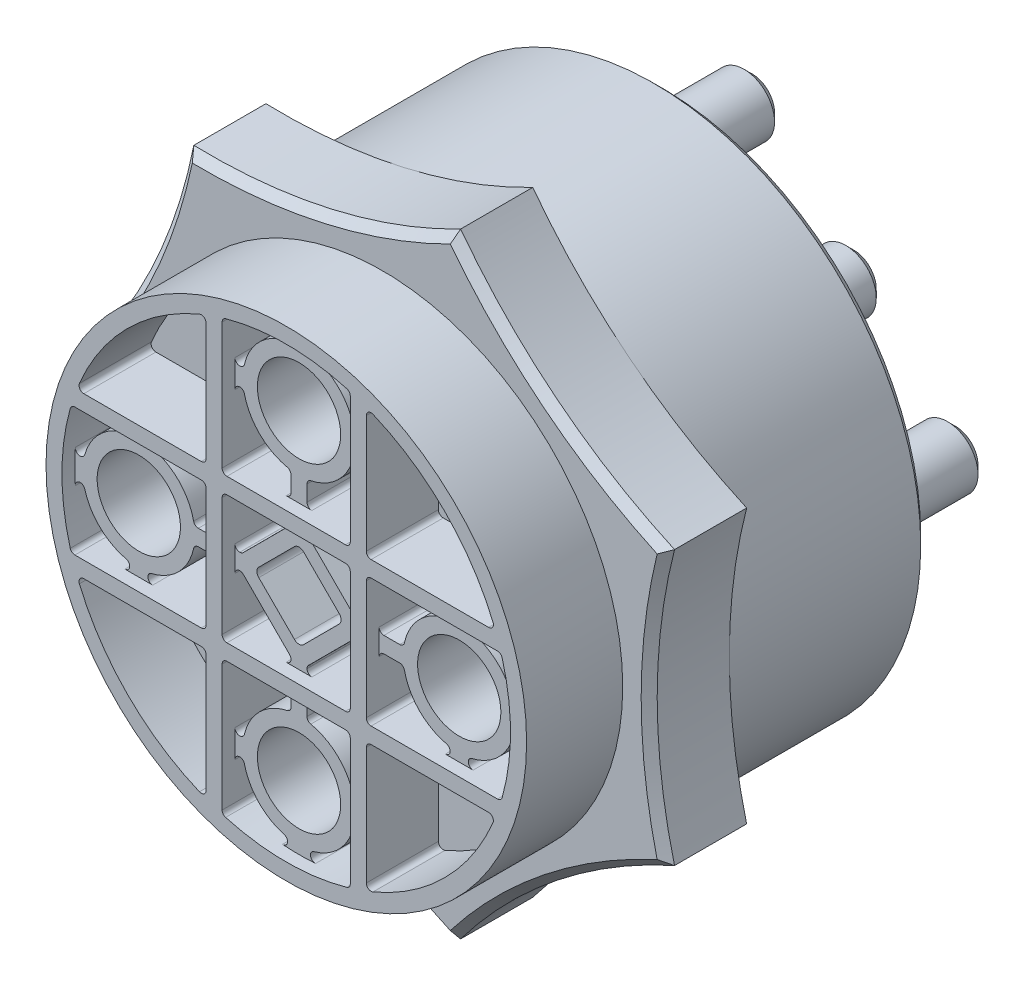
SolidWorks part; units mm, degrees
ref_plane "Front Plane" through (0, 0, 0) normal (0, 0, 1) x (1, 0, 0)
ref_plane "Top Plane" through (0, 0, 0) normal (0, 1, 0) x (1, 0, 0)
ref_plane "Right Plane" through (0, 0, 0) normal (1, 0, 0) x (0, 0, -1)
sketch "Sketch1" plane through (0, 0, 0) normal (0, 0, 1) x (1, 0, 0)
  circle A0 centre (0, 0) radius 16.85 construction
  circle A1 centre (0, 0) radius 16.65
  arc A2 (3.175, -6.35) -> (9.525, -6.35) centre (6.35, -6.35) ccw construction
  arc A3 (0, -15.875) -> (0, -9.525) centre (0, -12.7) ccw construction
  arc A4 (0, 4) -> (0, -4) centre (0, 0) ccw construction
  arc A5 (-6.35, -9.525) -> (-6.35, -3.175) centre (-6.35, -6.35) ccw construction
  arc A6 (-12.7, -3.175) -> (-12.7, 3.175) centre (-12.7, 0) ccw construction
  arc A7 (-6.35, 3.175) -> (-6.35, 9.525) centre (-6.35, 6.35) ccw construction
  arc A8 (15.875, 0) -> (9.525, 0) centre (12.7, 0) ccw construction
  arc A9 (9.525, 6.35) -> (3.175, 6.35) centre (6.35, 6.35) ccw construction
  arc A10 (3.175, 12.7) -> (-3.175, 12.7) centre (0, 12.7) ccw construction
  circle A11 centre (6.35, -6.35) radius 3.175 construction
  circle A12 centre (0, -12.7) radius 3.175 construction
  circle A13 centre (0, 0) radius 4 construction
  circle A14 centre (-6.35, -6.35) radius 3.175 construction
  circle A15 centre (-12.7, 0) radius 3.175 construction
  circle A16 centre (-6.35, 6.35) radius 3.175 construction
  circle A17 centre (12.7, 0) radius 3.175 construction
  circle A18 centre (6.35, 6.35) radius 3.175 construction
  circle A19 centre (0, 12.7) radius 3.175 construction
  circle A20 centre (-6.35, 6.35) radius 3.275
  circle A21 centre (-12.7, 0) radius 3.275
  circle A22 centre (-6.35, -6.35) radius 3.275
  circle A23 centre (0, 0) radius 4.1
  circle A24 centre (0, 12.7) radius 3.275
  circle A25 centre (6.35, 6.35) radius 3.275
  circle A26 centre (12.7, 0) radius 3.275
  circle A27 centre (6.35, -6.35) radius 3.275
  circle A28 centre (0, -12.7) radius 3.275
  arc A29 (-12.4359, 15.5945) -> (4.4391, 19.4457) centre (-11.3095, 49.5559) ccw construction
  dimension "D1" = 0.2
  dimension "D2" = 0.1
extrude "Boss-Extrude1" add sketch "Sketch1" along normal offset from surface (2.375 mm away) 0.2 offset beyond the face yes
sketch "Sketch2" plane through (0, 0, 2.375) normal (0, 0, 1) x (1, 0, 0)
  circle A0 centre (0, 0) radius 16.65 construction
  circle A1 centre (0, 0) radius 16.65
extrude "Boss-Extrude2" add sketch "Sketch2" along normal up to surface (22.075 mm away)
sketch "Sketch3" plane through (0, 0, 24.45) normal (0, 0, 1) x (1, 0, 0)
  circle A0 centre (0, 0) radius 15
  circle A1 centre (0, 0) radius 16.65 construction
  circle A2 centre (0, 0) radius 16.65
  dimension "D1" = 30
extrude "Cut-Extrude1" cut sketch "Sketch3" against normal blind 10
sketch "Sketch4" plane through (0, 0, 24.45) normal (0, 0, 1) x (1, 0, 0)
  line L0 (-13.1976, -3.971) -> (-5.3067, -3.971)
  line L1 (-5.3067, 4.029) -> (-13.1976, 4.029)
  line L2 (-5.0067, -3.671) -> (-5.0067, 3.729)
  line L3 (-12.64, 5.029) -> (-5.3067, 5.029)
  line L4 (-5.0067, 5.329) -> (-5.0067, 12.6623)
  line L5 (-5.3067, -4.971) -> (-12.64, -4.971)
  line L6 (-5.0067, -12.6043) -> (-5.0067, -5.271)
  line L7 (3.9933, -13.1619) -> (3.9933, -5.271)
  line L8 (-4.0067, -5.271) -> (-4.0067, -13.1619)
  line L9 (3.6933, -4.971) -> (-3.7067, -4.971)
  line L10 (-3.7067, -3.971) -> (3.6933, -3.971)
  line L11 (-4.0067, 3.729) -> (-4.0067, -3.671)
  line L12 (3.6933, 4.029) -> (-3.7067, 4.029)
  line L13 (3.9933, -3.671) -> (3.9933, 3.729)
  line L14 (-3.7067, 5.029) -> (3.6933, 5.029)
  line L15 (-4.0067, 13.2199) -> (-4.0067, 5.329)
  line L16 (3.9933, 5.329) -> (3.9933, 13.2199)
  line L17 (5.2933, 5.029) -> (12.6266, 5.029)
  line L18 (4.9933, 12.6623) -> (4.9933, 5.329)
  line L19 (4.9933, 3.729) -> (4.9933, -3.671)
  line L20 (13.1842, 4.029) -> (5.2933, 4.029)
  line L21 (5.2933, -3.971) -> (13.1842, -3.971)
  line L22 (12.6266, -4.971) -> (5.2933, -4.971)
  line L23 (4.9933, -5.271) -> (4.9933, -12.6043)
  line L24 (5.2933, -0.471) -> (6.2784, -0.471)
  line L25 (4.9933, 0.829) -> (4.9933, -0.771)
  line L26 (6.2784, 0.529) -> (5.2933, 0.529)
  line L27 (10.8593, 4.029) -> (9.1273, 4.029)
  line L28 (9.1273, -3.971) -> (10.8593, -3.971)
  line L29 (0.4933, 5.329) -> (0.4933, 6.3142)
  line L30 (-0.8067, 5.029) -> (0.7933, 5.029)
  line L31 (-0.5067, 6.3142) -> (-0.5067, 5.329)
  line L32 (-4.0067, 10.895) -> (-4.0067, 9.163)
  line L33 (3.9933, 9.163) -> (3.9933, 10.895)
  line L34 (-0.5067, -3.6611) -> (-0.5067, -3.671)
  line L35 (-3.4847, -0.5589) -> (-0.5946, -3.449)
  line L36 (-3.7067, -0.471) -> (-3.6968, -0.471)
  line L37 (-4.0067, 0.829) -> (-4.0067, -0.771)
  line L38 (-3.6968, 0.529) -> (-3.7067, 0.529)
  line L39 (-0.5946, 3.507) -> (-3.4847, 0.6169)
  line L40 (-0.5067, 3.729) -> (-0.5067, 3.7191)
  line L41 (0.7933, 4.029) -> (-0.8067, 4.029)
  line L42 (0.4933, 3.7191) -> (0.4933, 3.729)
  line L43 (3.4713, 0.6169) -> (0.5811, 3.507)
  line L44 (3.6933, 0.529) -> (3.6834, 0.529)
  line L45 (3.9933, -0.771) -> (3.9933, 0.829)
  line L46 (3.6834, -0.471) -> (3.6933, -0.471)
  line L47 (0.5811, -3.449) -> (3.4713, -0.5589)
  line L48 (0.4933, -3.671) -> (0.4933, -3.6611)
  line L49 (-0.8067, -3.971) -> (0.7933, -3.971)
  line L50 (-0.5067, -5.271) -> (-0.5067, -6.2561)
  line L51 (0.7933, -4.971) -> (-0.8067, -4.971)
  line L52 (0.4933, -6.2561) -> (0.4933, -5.271)
  line L53 (3.9933, -10.837) -> (3.9933, -9.105)
  line L54 (-4.0067, -9.105) -> (-4.0067, -10.837)
  line L55 (-5.3067, 0.529) -> (-6.2919, 0.529)
  line L56 (-5.0067, -0.771) -> (-5.0067, 0.829)
  line L57 (-6.2919, -0.471) -> (-5.3067, -0.471)
  line L58 (-10.8727, -3.971) -> (-9.1407, -3.971)
  line L59 (-9.1407, 4.029) -> (-10.8727, 4.029)
  line L60 (-2.4462, -0.1831) -> (-0.2189, -2.4105)
  line L61 (0.2054, -2.4105) -> (2.4328, -0.1831)
  line L62 (2.4328, 0.2411) -> (0.2054, 2.4685)
  line L63 (-0.2189, 2.4685) -> (-2.4462, 0.2411)
  circle A0 centre (0, 0) radius 14 construction
  circle A1 centre (0, 0) radius 15 construction
  arc A2 (-0.0067, 14.929) -> (14.3537, -3.9443) centre (-0.0067, 0.029) ccw
  arc A3 (14.3537, -3.9443) -> (-0.0067, 14.929) centre (-0.0067, 0.029) ccw
  arc A4 (-5.3067, -3.971) -> (-5.0067, -3.671) centre (-5.3067, -3.671) ccw
  arc A5 (-13.4865, -3.752) -> (-13.1976, -3.971) centre (-13.1976, -3.671) ccw
  arc A6 (-13.4865, 3.81) -> (-13.4865, -3.752) centre (-0.0067, 0.029) ccw
  arc A7 (-13.1976, 4.029) -> (-13.4865, 3.81) centre (-13.1976, 3.729) ccw
  arc A8 (-5.0067, 3.729) -> (-5.3067, 4.029) centre (-5.3067, 3.729) ccw
  arc A9 (-12.9166, 5.4451) -> (-12.64, 5.029) centre (-12.64, 5.329) ccw
  arc A10 (-5.4228, 12.9389) -> (-12.9166, 5.4451) centre (-0.0067, 0.029) ccw
  arc A11 (-5.0067, 12.6623) -> (-5.4228, 12.9389) centre (-5.3067, 12.6623) ccw
  arc A12 (-5.3067, 5.029) -> (-5.0067, 5.329) centre (-5.3067, 5.329) ccw
  arc A13 (-5.4228, -12.8809) -> (-5.0067, -12.6043) centre (-5.3067, -12.6043) ccw
  arc A14 (-12.9166, -5.387) -> (-5.4228, -12.8809) centre (-0.0067, 0.029) ccw
  arc A15 (-12.64, -4.971) -> (-12.9166, -5.387) centre (-12.64, -5.271) ccw
  arc A16 (-5.0067, -5.271) -> (-5.3067, -4.971) centre (-5.3067, -5.271) ccw
  arc A17 (3.9933, -5.271) -> (3.6933, -4.971) centre (3.6933, -5.271) ccw
  arc A18 (3.7743, -13.4507) -> (3.9933, -13.1619) centre (3.6933, -13.1619) ccw
  arc A19 (-3.7877, -13.4507) -> (3.7743, -13.4507) centre (-0.0067, 0.029) ccw
  arc A20 (-4.0067, -13.1619) -> (-3.7877, -13.4507) centre (-3.7067, -13.1619) ccw
  arc A21 (-3.7067, -4.971) -> (-4.0067, -5.271) centre (-3.7067, -5.271) ccw
  arc A22 (-4.0067, -3.671) -> (-3.7067, -3.971) centre (-3.7067, -3.671) ccw
  arc A23 (-3.7067, 4.029) -> (-4.0067, 3.729) centre (-3.7067, 3.729) ccw
  arc A24 (3.9933, 3.729) -> (3.6933, 4.029) centre (3.6933, 3.729) ccw
  arc A25 (3.6933, -3.971) -> (3.9933, -3.671) centre (3.6933, -3.671) ccw
  arc A26 (-4.0067, 5.329) -> (-3.7067, 5.029) centre (-3.7067, 5.329) ccw
  arc A27 (-3.7877, 13.5088) -> (-4.0067, 13.2199) centre (-3.7067, 13.2199) ccw
  arc A28 (3.7743, 13.5088) -> (-3.7877, 13.5088) centre (-0.0067, 0.029) ccw
  arc A29 (3.9933, 13.2199) -> (3.7743, 13.5088) centre (3.6933, 13.2199) ccw
  arc A30 (3.6933, 5.029) -> (3.9933, 5.329) centre (3.6933, 5.329) ccw
  arc A31 (5.4093, 12.9389) -> (4.9933, 12.6623) centre (5.2933, 12.6623) ccw
  arc A32 (12.9032, 5.4451) -> (5.4093, 12.9389) centre (-0.0067, 0.029) ccw
  arc A33 (12.6266, 5.029) -> (12.9032, 5.4451) centre (12.6266, 5.329) ccw
  arc A34 (4.9933, 5.329) -> (5.2933, 5.029) centre (5.2933, 5.329) ccw
  arc A35 (5.2933, 4.029) -> (4.9933, 3.729) centre (5.2933, 3.729) ccw
  arc A36 (13.473, 3.81) -> (13.1842, 4.029) centre (13.1842, 3.729) ccw
  arc A37 (13.473, -3.752) -> (13.473, 3.81) centre (-0.0067, 0.029) ccw
  arc A38 (13.1842, -3.971) -> (13.473, -3.752) centre (13.1842, -3.671) ccw
  arc A39 (4.9933, -3.671) -> (5.2933, -3.971) centre (5.2933, -3.671) ccw
  arc A40 (12.9032, -5.387) -> (12.6266, -4.971) centre (12.6266, -5.271) ccw
  arc A41 (5.4093, -12.8809) -> (12.9032, -5.387) centre (-0.0067, 0.029) ccw
  arc A42 (4.9933, -12.6043) -> (5.4093, -12.8809) centre (5.2933, -12.6043) ccw
  arc A43 (5.2933, -4.971) -> (4.9933, -5.271) centre (5.2933, -5.271) ccw
  circle A44 centre (-0.0067, -9.971) radius 2.5
  circle A45 centre (-10.0067, 0.029) radius 2.5
  circle A46 centre (9.9933, 0.029) radius 2.5
  circle A47 centre (-0.0067, 10.029) radius 2.5
  arc A48 (5.2933, -0.471) -> (4.9933, -0.771) centre (5.2933, -0.771) ccw
  arc A49 (4.9933, 0.829) -> (5.2933, 0.529) centre (5.2933, 0.829) ccw
  arc A50 (6.2784, 0.529) -> (6.5717, 0.7659) centre (6.2784, 0.829) ccw
  arc A51 (9.1956, 3.4369) -> (6.5717, 0.7659) centre (9.9933, 0.029) ccw
  arc A52 (9.1956, 3.4369) -> (9.1273, 4.029) centre (9.1273, 3.729) ccw
  arc A53 (10.8593, 4.029) -> (10.7909, 3.4369) centre (10.8593, 3.729) ccw
  arc A54 (13.3666, 0.962) -> (10.7909, 3.4369) centre (9.9933, 0.029) ccw
  arc A55 (13.3666, 0.962) -> (13.955, 1.0642) centre (13.6558, 1.042) ccw
  arc A56 (13.955, -1.0061) -> (13.955, 1.0642) centre (-0.0067, 0.029) ccw
  arc A57 (13.955, -1.0061) -> (13.3666, -0.904) centre (13.6558, -0.9839) ccw
  arc A58 (10.7909, -3.3789) -> (13.3666, -0.904) centre (9.9933, 0.029) ccw
  arc A59 (10.7909, -3.3789) -> (10.8593, -3.971) centre (10.8593, -3.671) ccw
  arc A60 (9.1273, -3.971) -> (9.1956, -3.3789) centre (9.1273, -3.671) ccw
  arc A61 (6.5717, -0.7078) -> (9.1956, -3.3789) centre (9.9933, 0.029) ccw
  arc A62 (6.5717, -0.7078) -> (6.2784, -0.471) centre (6.2784, -0.771) ccw
  arc A63 (-0.5067, -3.6611) -> (-0.5946, -3.449) centre (-0.8067, -3.6611) ccw
  arc A64 (-3.4847, -0.5589) -> (-3.6968, -0.471) centre (-3.6968, -0.771) ccw
  arc A65 (-3.7067, -0.471) -> (-4.0067, -0.771) centre (-3.7067, -0.771) ccw
  arc A66 (-4.0067, 0.829) -> (-3.7067, 0.529) centre (-3.7067, 0.829) ccw
  arc A67 (-3.6968, 0.529) -> (-3.4847, 0.6169) centre (-3.6968, 0.829) ccw
  arc A68 (-0.5946, 3.507) -> (-0.5067, 3.7191) centre (-0.8067, 3.7191) ccw
  arc A69 (-0.5067, 3.729) -> (-0.8067, 4.029) centre (-0.8067, 3.729) ccw
  arc A70 (0.7933, 4.029) -> (0.4933, 3.729) centre (0.7933, 3.729) ccw
  arc A71 (0.4933, 3.7191) -> (0.5811, 3.507) centre (0.7933, 3.7191) ccw
  arc A72 (3.4713, 0.6169) -> (3.6834, 0.529) centre (3.6834, 0.829) ccw
  arc A73 (3.6933, 0.529) -> (3.9933, 0.829) centre (3.6933, 0.829) ccw
  arc A74 (3.9933, -0.771) -> (3.6933, -0.471) centre (3.6933, -0.771) ccw
  arc A75 (3.6834, -0.471) -> (3.4713, -0.5589) centre (3.6834, -0.771) ccw
  arc A76 (0.5811, -3.449) -> (0.4933, -3.6611) centre (0.7933, -3.6611) ccw
  arc A77 (0.4933, -3.671) -> (0.7933, -3.971) centre (0.7933, -3.671) ccw
  arc A78 (-0.8067, -3.971) -> (-0.5067, -3.671) centre (-0.8067, -3.671) ccw
  arc A79 (0.4933, 5.329) -> (0.7933, 5.029) centre (0.7933, 5.329) ccw
  arc A80 (-0.8067, 5.029) -> (-0.5067, 5.329) centre (-0.8067, 5.329) ccw
  arc A81 (-0.5067, 6.3142) -> (-0.7436, 6.6075) centre (-0.8067, 6.3142) ccw
  arc A82 (-3.4146, 9.2314) -> (-0.7436, 6.6075) centre (-0.0067, 10.029) ccw
  arc A83 (-3.4146, 9.2314) -> (-4.0067, 9.163) centre (-3.7067, 9.163) ccw
  arc A84 (-4.0067, 10.895) -> (-3.4146, 10.8267) centre (-3.7067, 10.895) ccw
  arc A85 (-0.9397, 13.4024) -> (-3.4146, 10.8267) centre (-0.0067, 10.029) ccw
  arc A86 (-0.9397, 13.4024) -> (-1.0419, 13.9907) centre (-1.0197, 13.6915) ccw
  arc A87 (1.0284, 13.9907) -> (-1.0419, 13.9907) centre (-0.0067, 0.029) ccw
  arc A88 (1.0284, 13.9907) -> (0.9263, 13.4024) centre (1.0062, 13.6915) ccw
  arc A89 (3.4012, 10.8267) -> (0.9263, 13.4024) centre (-0.0067, 10.029) ccw
  arc A90 (3.4012, 10.8267) -> (3.9933, 10.895) centre (3.6933, 10.895) ccw
  arc A91 (3.9933, 9.163) -> (3.4012, 9.2314) centre (3.6933, 9.163) ccw
  arc A92 (0.7301, 6.6075) -> (3.4012, 9.2314) centre (-0.0067, 10.029) ccw
  arc A93 (0.7301, 6.6075) -> (0.4933, 6.3142) centre (0.7933, 6.3142) ccw
  arc A94 (-0.5067, -5.271) -> (-0.8067, -4.971) centre (-0.8067, -5.271) ccw
  arc A95 (0.7933, -4.971) -> (0.4933, -5.271) centre (0.7933, -5.271) ccw
  arc A96 (0.4933, -6.2561) -> (0.7301, -6.5494) centre (0.7933, -6.2561) ccw
  arc A97 (3.4012, -9.1733) -> (0.7301, -6.5494) centre (-0.0067, -9.971) ccw
  arc A98 (3.4012, -9.1733) -> (3.9933, -9.105) centre (3.6933, -9.105) ccw
  arc A99 (3.9933, -10.837) -> (3.4012, -10.7686) centre (3.6933, -10.837) ccw
  arc A100 (0.9263, -13.3443) -> (3.4012, -10.7686) centre (-0.0067, -9.971) ccw
  arc A101 (0.9263, -13.3443) -> (1.0284, -13.9327) centre (1.0062, -13.6335) ccw
  arc A102 (-1.0419, -13.9327) -> (1.0284, -13.9327) centre (-0.0067, 0.029) ccw
  arc A103 (-1.0419, -13.9327) -> (-0.9397, -13.3443) centre (-1.0197, -13.6335) ccw
  arc A104 (-3.4146, -10.7686) -> (-0.9397, -13.3443) centre (-0.0067, -9.971) ccw
  arc A105 (-3.4146, -10.7686) -> (-4.0067, -10.837) centre (-3.7067, -10.837) ccw
  arc A106 (-4.0067, -9.105) -> (-3.4146, -9.1733) centre (-3.7067, -9.105) ccw
  arc A107 (-0.7436, -6.5494) -> (-3.4146, -9.1733) centre (-0.0067, -9.971) ccw
  arc A108 (-0.7436, -6.5494) -> (-0.5067, -6.2561) centre (-0.8067, -6.2561) ccw
  arc A109 (-5.3067, 0.529) -> (-5.0067, 0.829) centre (-5.3067, 0.829) ccw
  arc A110 (-5.0067, -0.771) -> (-5.3067, -0.471) centre (-5.3067, -0.771) ccw
  arc A111 (-6.2919, -0.471) -> (-6.5852, -0.7078) centre (-6.2919, -0.771) ccw
  arc A112 (-9.2091, -3.3789) -> (-6.5852, -0.7078) centre (-10.0067, 0.029) ccw
  arc A113 (-9.2091, -3.3789) -> (-9.1407, -3.971) centre (-9.1407, -3.671) ccw
  arc A114 (-10.8727, -3.971) -> (-10.8044, -3.3789) centre (-10.8727, -3.671) ccw
  arc A115 (-13.3801, -0.904) -> (-10.8044, -3.3789) centre (-10.0067, 0.029) ccw
  arc A116 (-13.3801, -0.904) -> (-13.9684, -1.0061) centre (-13.6692, -0.9839) ccw
  arc A117 (-13.9684, 1.0642) -> (-13.9684, -1.0061) centre (-0.0067, 0.029) ccw
  arc A118 (-13.9684, 1.0642) -> (-13.3801, 0.962) centre (-13.6692, 1.042) ccw
  arc A119 (-10.8044, 3.4369) -> (-13.3801, 0.962) centre (-10.0067, 0.029) ccw
  arc A120 (-10.8044, 3.4369) -> (-10.8727, 4.029) centre (-10.8727, 3.729) ccw
  arc A121 (-9.1407, 4.029) -> (-9.2091, 3.4369) centre (-9.1407, 3.729) ccw
  arc A122 (-6.5852, 0.7659) -> (-9.2091, 3.4369) centre (-10.0067, 0.029) ccw
  arc A123 (-6.5852, 0.7659) -> (-6.2919, 0.529) centre (-6.2919, 0.829) ccw
  arc A124 (-0.2189, -2.4105) -> (0.2054, -2.4105) centre (-0.0067, -2.1984) ccw
  arc A125 (2.4328, -0.1831) -> (2.4328, 0.2411) centre (2.2207, 0.029) ccw
  arc A126 (0.2054, 2.4685) -> (-0.2189, 2.4685) centre (-0.0067, 2.2564) ccw
  arc A127 (-2.4462, 0.2411) -> (-2.4462, -0.1831) centre (-2.2341, 0.029) ccw
  circle A128 centre (-0.0067, 0.029) radius 15 construction
  dimension "D1" = 1
  dimension "D4" = 0.9
  dimension "D13" = 5
  dimension "D14" = 1
  dimension "D15" = 30
  dimension "D2" = 5
  dimension "D3" = 10
  dimension "D5" = 1
  dimension "D6" = 1
  dimension "D7" = 1
  dimension "D8" = 1
  dimension "D9" = 8
  dimension "D10" = 4
  dimension "D11" = 10
  dimension "D12" = 10
sketch "Sketch6" plane through (0, 0, 24.45) normal (0, 0, 1) x (1, 0, 0)
  line L2 (-5.3067, -4.971) -> (-12.64, -4.971)
  line L3 (-5.3067, 4.029) -> (-13.1976, 4.029)
  line L4 (-13.1976, -3.971) -> (-5.3067, -3.971)
  line L5 (-5.0067, -3.671) -> (-5.0067, 3.729)
  line L6 (-5.3067, 4.029) -> (-13.1976, 4.029)
  line L7 (-13.1976, -3.971) -> (-5.3067, -3.971)
  line L8 (-5.0067, -3.671) -> (-5.0067, 3.729)
  line L9 (-5.0067, -12.6043) -> (-5.0067, -5.271)
  line L10 (-5.3067, -4.971) -> (-12.64, -4.971)
  line L11 (-5.0067, -12.6043) -> (-5.0067, -5.271)
  line L12 (-5.0067, 5.329) -> (-5.0067, 12.6623)
  line L13 (-12.64, 5.029) -> (-5.3067, 5.029)
  line L14 (-5.0067, 5.329) -> (-5.0067, 12.6623)
  line L15 (-12.64, 5.029) -> (-5.3067, 5.029)
  line L16 (5.2933, 5.029) -> (12.6266, 5.029)
  line L17 (-4.0067, -5.271) -> (-4.0067, -13.1619)
  line L18 (-0.2189, 2.4685) -> (-2.4462, 0.2411)
  line L19 (2.4328, 0.2411) -> (0.2054, 2.4685)
  line L20 (0.2054, -2.4105) -> (2.4328, -0.1831)
  line L21 (-2.4462, -0.1831) -> (-0.2189, -2.4105)
  line L22 (-0.2189, 2.4685) -> (-2.4462, 0.2411)
  line L23 (2.4328, 0.2411) -> (0.2054, 2.4685)
  line L24 (0.2054, -2.4105) -> (2.4328, -0.1831)
  line L25 (-2.4462, -0.1831) -> (-0.2189, -2.4105)
  line L26 (3.9933, -13.1619) -> (3.9933, -5.271)
  line L27 (3.6933, -4.971) -> (-3.7067, -4.971)
  line L28 (-4.0067, -5.271) -> (-4.0067, -13.1619)
  line L29 (3.9933, -13.1619) -> (3.9933, -5.271)
  line L30 (3.6933, -4.971) -> (-3.7067, -4.971)
  line L31 (4.9933, 12.6623) -> (4.9933, 5.329)
  line L32 (3.9933, -3.671) -> (3.9933, 3.729)
  line L33 (-3.7067, -3.971) -> (3.6933, -3.971)
  line L34 (-4.0067, 3.729) -> (-4.0067, -3.671)
  line L35 (3.6933, 4.029) -> (-3.7067, 4.029)
  line L36 (3.9933, -3.671) -> (3.9933, 3.729)
  line L37 (-3.7067, -3.971) -> (3.6933, -3.971)
  line L38 (-4.0067, 3.729) -> (-4.0067, -3.671)
  line L39 (3.6933, 4.029) -> (-3.7067, 4.029)
  line L40 (5.2933, 5.029) -> (12.6266, 5.029)
  line L41 (4.9933, 12.6623) -> (4.9933, 5.329)
  line L42 (4.9933, -5.271) -> (4.9933, -12.6043)
  line L43 (3.9933, 5.329) -> (3.9933, 13.2199)
  line L44 (-4.0067, 13.2199) -> (-4.0067, 5.329)
  line L45 (-3.7067, 5.029) -> (3.6933, 5.029)
  line L46 (3.9933, 5.329) -> (3.9933, 13.2199)
  line L47 (-4.0067, 13.2199) -> (-4.0067, 5.329)
  line L48 (-3.7067, 5.029) -> (3.6933, 5.029)
  line L49 (5.2933, -3.971) -> (13.1842, -3.971)
  line L50 (4.9933, 3.729) -> (4.9933, -3.671)
  line L51 (13.1842, 4.029) -> (5.2933, 4.029)
  line L52 (5.2933, -3.971) -> (13.1842, -3.971)
  line L53 (4.9933, 3.729) -> (4.9933, -3.671)
  line L54 (13.1842, 4.029) -> (5.2933, 4.029)
  line L55 (12.6266, -4.971) -> (5.2933, -4.971)
  line L56 (4.9933, -5.271) -> (4.9933, -12.6043)
  line L57 (12.6266, -4.971) -> (5.2933, -4.971)
  line L61 (5.2933, -0.471) -> (6.2784, -0.471)
  line L62 (4.9933, 0.829) -> (4.9933, -0.771)
  line L63 (6.2784, 0.529) -> (5.2933, 0.529)
  line L64 (10.8593, 4.029) -> (9.1273, 4.029)
  line L65 (9.1273, -3.971) -> (10.8593, -3.971)
  line L66 (5.2933, -0.471) -> (6.2784, -0.471)
  line L67 (4.9933, 0.829) -> (4.9933, -0.771)
  line L68 (6.2784, 0.529) -> (5.2933, 0.529)
  line L69 (10.8593, 4.029) -> (9.1273, 4.029)
  line L70 (9.1273, -3.971) -> (10.8593, -3.971)
  line L71 (0.4933, 5.329) -> (0.4933, 6.3142)
  line L72 (-0.8067, 5.029) -> (0.7933, 5.029)
  line L73 (-0.5067, 6.3142) -> (-0.5067, 5.329)
  line L74 (-4.0067, 10.895) -> (-4.0067, 9.163)
  line L75 (3.9933, 9.163) -> (3.9933, 10.895)
  line L76 (0.4933, 5.329) -> (0.4933, 6.3142)
  line L77 (-0.8067, 5.029) -> (0.7933, 5.029)
  line L78 (-0.5067, 6.3142) -> (-0.5067, 5.329)
  line L79 (-4.0067, 10.895) -> (-4.0067, 9.163)
  line L80 (3.9933, 9.163) -> (3.9933, 10.895)
  line L81 (-4.0067, -9.105) -> (-4.0067, -10.837)
  line L82 (-0.5067, -3.6611) -> (-0.5067, -3.671)
  line L83 (-3.4847, -0.5589) -> (-0.5946, -3.449)
  line L84 (-3.7067, -0.471) -> (-3.6968, -0.471)
  line L85 (-4.0067, 0.829) -> (-4.0067, -0.771)
  line L86 (-3.6968, 0.529) -> (-3.7067, 0.529)
  line L87 (-0.5946, 3.507) -> (-3.4847, 0.6169)
  line L88 (-0.5067, 3.729) -> (-0.5067, 3.7191)
  line L89 (0.7933, 4.029) -> (-0.8067, 4.029)
  line L90 (0.4933, 3.7191) -> (0.4933, 3.729)
  line L91 (3.4713, 0.6169) -> (0.5811, 3.507)
  line L92 (3.6933, 0.529) -> (3.6834, 0.529)
  line L93 (3.9933, -0.771) -> (3.9933, 0.829)
  line L94 (3.6834, -0.471) -> (3.6933, -0.471)
  line L95 (0.5811, -3.449) -> (3.4713, -0.5589)
  line L96 (0.4933, -3.671) -> (0.4933, -3.6611)
  line L97 (-0.8067, -3.971) -> (0.7933, -3.971)
  line L98 (-0.5067, -3.6611) -> (-0.5067, -3.671)
  line L99 (-3.4847, -0.5589) -> (-0.5946, -3.449)
  line L100 (-3.7067, -0.471) -> (-3.6968, -0.471)
  line L101 (-4.0067, 0.829) -> (-4.0067, -0.771)
  line L102 (-3.6968, 0.529) -> (-3.7067, 0.529)
  line L103 (-0.5946, 3.507) -> (-3.4847, 0.6169)
  line L104 (-0.5067, 3.729) -> (-0.5067, 3.7191)
  line L105 (0.7933, 4.029) -> (-0.8067, 4.029)
  line L106 (0.4933, 3.7191) -> (0.4933, 3.729)
  line L107 (3.4713, 0.6169) -> (0.5811, 3.507)
  line L108 (3.6933, 0.529) -> (3.6834, 0.529)
  line L109 (3.9933, -0.771) -> (3.9933, 0.829)
  line L110 (3.6834, -0.471) -> (3.6933, -0.471)
  line L111 (0.5811, -3.449) -> (3.4713, -0.5589)
  line L112 (0.4933, -3.671) -> (0.4933, -3.6611)
  line L113 (-0.8067, -3.971) -> (0.7933, -3.971)
  line L114 (-0.5067, -5.271) -> (-0.5067, -6.2561)
  line L115 (0.7933, -4.971) -> (-0.8067, -4.971)
  line L116 (0.4933, -6.2561) -> (0.4933, -5.271)
  line L117 (3.9933, -10.837) -> (3.9933, -9.105)
  line L118 (-4.0067, -9.105) -> (-4.0067, -10.837)
  line L119 (-0.5067, -5.271) -> (-0.5067, -6.2561)
  line L120 (0.7933, -4.971) -> (-0.8067, -4.971)
  line L121 (0.4933, -6.2561) -> (0.4933, -5.271)
  line L122 (3.9933, -10.837) -> (3.9933, -9.105)
  line L123 (-6.2919, -0.471) -> (-5.3067, -0.471)
  line L124 (-10.8727, -3.971) -> (-9.1407, -3.971)
  line L125 (-9.1407, 4.029) -> (-10.8727, 4.029)
  line L126 (-5.3067, 0.529) -> (-6.2919, 0.529)
  line L127 (-5.0067, -0.771) -> (-5.0067, 0.829)
  line L128 (-6.2919, -0.471) -> (-5.3067, -0.471)
  line L129 (-10.8727, -3.971) -> (-9.1407, -3.971)
  line L130 (-9.1407, 4.029) -> (-10.8727, 4.029)
  line L131 (-5.3067, 0.529) -> (-6.2919, 0.529)
  line L132 (-5.0067, -0.771) -> (-5.0067, 0.829)
  circle A1 centre (-0.0067, 10.029) radius 2.5
  arc A2 (-0.0067, 14.929) -> (14.3537, -3.9443) centre (-0.0067, 0.029) ccw
  arc A3 (14.3537, -3.9443) -> (-0.0067, 14.929) centre (-0.0067, 0.029) ccw
  arc A4 (-0.0067, 14.929) -> (14.3537, -3.9443) centre (-0.0067, 0.029) ccw
  arc A5 (14.3537, -3.9443) -> (-0.0067, 14.929) centre (-0.0067, 0.029) ccw
  circle A6 centre (-0.0067, 10.029) radius 2.5
  circle A7 centre (9.9933, 0.029) radius 2.5
  circle A8 centre (9.9933, 0.029) radius 2.5
  circle A9 centre (-10.0067, 0.029) radius 2.5
  circle A10 centre (-10.0067, 0.029) radius 2.5
  circle A11 centre (-0.0067, -9.971) radius 2.5
  circle A12 centre (-0.0067, -9.971) radius 2.5
  arc A16 (-12.64, -4.971) -> (-12.9166, -5.387) centre (-12.64, -5.271) ccw
  arc A17 (-13.1976, 4.029) -> (-13.4865, 3.81) centre (-13.1976, 3.729) ccw
  arc A18 (-13.4865, 3.81) -> (-13.4865, -3.752) centre (-0.0067, 0.029) ccw
  arc A19 (-13.4865, -3.752) -> (-13.1976, -3.971) centre (-13.1976, -3.671) ccw
  arc A20 (-5.3067, -3.971) -> (-5.0067, -3.671) centre (-5.3067, -3.671) ccw
  arc A21 (-5.0067, 3.729) -> (-5.3067, 4.029) centre (-5.3067, 3.729) ccw
  arc A22 (-13.1976, 4.029) -> (-13.4865, 3.81) centre (-13.1976, 3.729) ccw
  arc A23 (-13.4865, 3.81) -> (-13.4865, -3.752) centre (-0.0067, 0.029) ccw
  arc A24 (-13.4865, -3.752) -> (-13.1976, -3.971) centre (-13.1976, -3.671) ccw
  arc A25 (-5.3067, -3.971) -> (-5.0067, -3.671) centre (-5.3067, -3.671) ccw
  arc A26 (-5.0067, 3.729) -> (-5.3067, 4.029) centre (-5.3067, 3.729) ccw
  arc A27 (-12.9166, -5.387) -> (-5.4228, -12.8809) centre (-0.0067, 0.029) ccw
  arc A28 (-5.4228, -12.8809) -> (-5.0067, -12.6043) centre (-5.3067, -12.6043) ccw
  arc A29 (-5.0067, -5.271) -> (-5.3067, -4.971) centre (-5.3067, -5.271) ccw
  arc A30 (-12.64, -4.971) -> (-12.9166, -5.387) centre (-12.64, -5.271) ccw
  arc A31 (-12.9166, -5.387) -> (-5.4228, -12.8809) centre (-0.0067, 0.029) ccw
  arc A32 (-5.4228, -12.8809) -> (-5.0067, -12.6043) centre (-5.3067, -12.6043) ccw
  arc A33 (-5.0067, -5.271) -> (-5.3067, -4.971) centre (-5.3067, -5.271) ccw
  arc A34 (-5.0067, 12.6623) -> (-5.4228, 12.9389) centre (-5.3067, 12.6623) ccw
  arc A35 (-5.4228, 12.9389) -> (-12.9166, 5.4451) centre (-0.0067, 0.029) ccw
  arc A36 (-12.9166, 5.4451) -> (-12.64, 5.029) centre (-12.64, 5.329) ccw
  arc A37 (-5.3067, 5.029) -> (-5.0067, 5.329) centre (-5.3067, 5.329) ccw
  arc A38 (-5.0067, 12.6623) -> (-5.4228, 12.9389) centre (-5.3067, 12.6623) ccw
  arc A39 (-5.4228, 12.9389) -> (-12.9166, 5.4451) centre (-0.0067, 0.029) ccw
  arc A40 (-12.9166, 5.4451) -> (-12.64, 5.029) centre (-12.64, 5.329) ccw
  arc A41 (-5.3067, 5.029) -> (-5.0067, 5.329) centre (-5.3067, 5.329) ccw
  arc A42 (0.2054, 2.4685) -> (-0.2189, 2.4685) centre (-0.0067, 2.2564) ccw
  arc A43 (2.4328, -0.1831) -> (2.4328, 0.2411) centre (2.2207, 0.029) ccw
  arc A44 (-0.2189, -2.4105) -> (0.2054, -2.4105) centre (-0.0067, -2.1984) ccw
  arc A45 (-2.4462, 0.2411) -> (-2.4462, -0.1831) centre (-2.2341, 0.029) ccw
  arc A46 (0.2054, 2.4685) -> (-0.2189, 2.4685) centre (-0.0067, 2.2564) ccw
  arc A47 (2.4328, -0.1831) -> (2.4328, 0.2411) centre (2.2207, 0.029) ccw
  arc A48 (-0.2189, -2.4105) -> (0.2054, -2.4105) centre (-0.0067, -2.1984) ccw
  arc A49 (-2.4462, 0.2411) -> (-2.4462, -0.1831) centre (-2.2341, 0.029) ccw
  arc A50 (3.9933, 3.729) -> (3.6933, 4.029) centre (3.6933, 3.729) ccw
  arc A51 (-4.0067, -13.1619) -> (-3.7877, -13.4507) centre (-3.7067, -13.1619) ccw
  arc A52 (-3.7877, -13.4507) -> (3.7743, -13.4507) centre (-0.0067, 0.029) ccw
  arc A53 (3.7743, -13.4507) -> (3.9933, -13.1619) centre (3.6933, -13.1619) ccw
  arc A54 (3.9933, -5.271) -> (3.6933, -4.971) centre (3.6933, -5.271) ccw
  arc A55 (-3.7067, -4.971) -> (-4.0067, -5.271) centre (-3.7067, -5.271) ccw
  arc A56 (-4.0067, -13.1619) -> (-3.7877, -13.4507) centre (-3.7067, -13.1619) ccw
  arc A57 (-3.7877, -13.4507) -> (3.7743, -13.4507) centre (-0.0067, 0.029) ccw
  arc A58 (3.7743, -13.4507) -> (3.9933, -13.1619) centre (3.6933, -13.1619) ccw
  arc A59 (3.9933, -5.271) -> (3.6933, -4.971) centre (3.6933, -5.271) ccw
  arc A60 (-3.7067, -4.971) -> (-4.0067, -5.271) centre (-3.7067, -5.271) ccw
  arc A61 (3.6933, -3.971) -> (3.9933, -3.671) centre (3.6933, -3.671) ccw
  arc A62 (-4.0067, -3.671) -> (-3.7067, -3.971) centre (-3.7067, -3.671) ccw
  arc A63 (-3.7067, 4.029) -> (-4.0067, 3.729) centre (-3.7067, 3.729) ccw
  arc A64 (3.9933, 3.729) -> (3.6933, 4.029) centre (3.6933, 3.729) ccw
  arc A65 (3.6933, -3.971) -> (3.9933, -3.671) centre (3.6933, -3.671) ccw
  arc A66 (-4.0067, -3.671) -> (-3.7067, -3.971) centre (-3.7067, -3.671) ccw
  arc A67 (-3.7067, 4.029) -> (-4.0067, 3.729) centre (-3.7067, 3.729) ccw
  arc A68 (12.6266, 5.029) -> (12.9032, 5.4451) centre (12.6266, 5.329) ccw
  arc A69 (12.9032, 5.4451) -> (5.4093, 12.9389) centre (-0.0067, 0.029) ccw
  arc A70 (5.4093, 12.9389) -> (4.9933, 12.6623) centre (5.2933, 12.6623) ccw
  arc A71 (4.9933, 5.329) -> (5.2933, 5.029) centre (5.2933, 5.329) ccw
  arc A72 (12.6266, 5.029) -> (12.9032, 5.4451) centre (12.6266, 5.329) ccw
  arc A73 (12.9032, 5.4451) -> (5.4093, 12.9389) centre (-0.0067, 0.029) ccw
  arc A74 (5.4093, 12.9389) -> (4.9933, 12.6623) centre (5.2933, 12.6623) ccw
  arc A75 (4.9933, 5.329) -> (5.2933, 5.029) centre (5.2933, 5.329) ccw
  arc A76 (4.9933, -12.6043) -> (5.4093, -12.8809) centre (5.2933, -12.6043) ccw
  arc A77 (3.9933, 13.2199) -> (3.7743, 13.5088) centre (3.6933, 13.2199) ccw
  arc A78 (3.7743, 13.5088) -> (-3.7877, 13.5088) centre (-0.0067, 0.029) ccw
  arc A79 (-3.7877, 13.5088) -> (-4.0067, 13.2199) centre (-3.7067, 13.2199) ccw
  arc A80 (-4.0067, 5.329) -> (-3.7067, 5.029) centre (-3.7067, 5.329) ccw
  arc A81 (3.6933, 5.029) -> (3.9933, 5.329) centre (3.6933, 5.329) ccw
  arc A82 (3.9933, 13.2199) -> (3.7743, 13.5088) centre (3.6933, 13.2199) ccw
  arc A83 (3.7743, 13.5088) -> (-3.7877, 13.5088) centre (-0.0067, 0.029) ccw
  arc A84 (-3.7877, 13.5088) -> (-4.0067, 13.2199) centre (-3.7067, 13.2199) ccw
  arc A85 (-4.0067, 5.329) -> (-3.7067, 5.029) centre (-3.7067, 5.329) ccw
  arc A86 (3.6933, 5.029) -> (3.9933, 5.329) centre (3.6933, 5.329) ccw
  arc A87 (13.473, 3.81) -> (13.1842, 4.029) centre (13.1842, 3.729) ccw
  arc A88 (13.473, -3.752) -> (13.473, 3.81) centre (-0.0067, 0.029) ccw
  arc A89 (13.1842, -3.971) -> (13.473, -3.752) centre (13.1842, -3.671) ccw
  arc A90 (4.9933, -3.671) -> (5.2933, -3.971) centre (5.2933, -3.671) ccw
  arc A91 (5.2933, 4.029) -> (4.9933, 3.729) centre (5.2933, 3.729) ccw
  arc A92 (13.473, 3.81) -> (13.1842, 4.029) centre (13.1842, 3.729) ccw
  arc A93 (13.473, -3.752) -> (13.473, 3.81) centre (-0.0067, 0.029) ccw
  arc A94 (13.1842, -3.971) -> (13.473, -3.752) centre (13.1842, -3.671) ccw
  arc A95 (4.9933, -3.671) -> (5.2933, -3.971) centre (5.2933, -3.671) ccw
  arc A96 (5.2933, 4.029) -> (4.9933, 3.729) centre (5.2933, 3.729) ccw
  arc A97 (5.4093, -12.8809) -> (12.9032, -5.387) centre (-0.0067, 0.029) ccw
  arc A98 (12.9032, -5.387) -> (12.6266, -4.971) centre (12.6266, -5.271) ccw
  arc A99 (5.2933, -4.971) -> (4.9933, -5.271) centre (5.2933, -5.271) ccw
  arc A100 (4.9933, -12.6043) -> (5.4093, -12.8809) centre (5.2933, -12.6043) ccw
  arc A101 (5.4093, -12.8809) -> (12.9032, -5.387) centre (-0.0067, 0.029) ccw
  arc A102 (12.9032, -5.387) -> (12.6266, -4.971) centre (12.6266, -5.271) ccw
  arc A103 (5.2933, -4.971) -> (4.9933, -5.271) centre (5.2933, -5.271) ccw
  arc A115 (6.5717, -0.7078) -> (9.1956, -3.3789) centre (9.9933, 0.029) ccw
  arc A116 (6.5717, -0.7078) -> (6.2784, -0.471) centre (6.2784, -0.771) ccw
  arc A117 (5.2933, -0.471) -> (4.9933, -0.771) centre (5.2933, -0.771) ccw
  arc A118 (4.9933, 0.829) -> (5.2933, 0.529) centre (5.2933, 0.829) ccw
  arc A119 (6.2784, 0.529) -> (6.5717, 0.7659) centre (6.2784, 0.829) ccw
  arc A120 (9.1956, 3.4369) -> (6.5717, 0.7659) centre (9.9933, 0.029) ccw
  arc A121 (9.1956, 3.4369) -> (9.1273, 4.029) centre (9.1273, 3.729) ccw
  arc A122 (10.8593, 4.029) -> (10.7909, 3.4369) centre (10.8593, 3.729) ccw
  arc A123 (13.3666, 0.962) -> (10.7909, 3.4369) centre (9.9933, 0.029) ccw
  arc A124 (13.3666, 0.962) -> (13.955, 1.0642) centre (13.6558, 1.042) ccw
  arc A125 (13.955, -1.0061) -> (13.955, 1.0642) centre (-0.0067, 0.029) ccw
  arc A126 (13.955, -1.0061) -> (13.3666, -0.904) centre (13.6558, -0.9839) ccw
  arc A127 (10.7909, -3.3789) -> (13.3666, -0.904) centre (9.9933, 0.029) ccw
  arc A128 (10.7909, -3.3789) -> (10.8593, -3.971) centre (10.8593, -3.671) ccw
  arc A129 (9.1273, -3.971) -> (9.1956, -3.3789) centre (9.1273, -3.671) ccw
  arc A130 (6.5717, -0.7078) -> (9.1956, -3.3789) centre (9.9933, 0.029) ccw
  arc A131 (6.5717, -0.7078) -> (6.2784, -0.471) centre (6.2784, -0.771) ccw
  arc A132 (5.2933, -0.471) -> (4.9933, -0.771) centre (5.2933, -0.771) ccw
  arc A133 (4.9933, 0.829) -> (5.2933, 0.529) centre (5.2933, 0.829) ccw
  arc A134 (6.2784, 0.529) -> (6.5717, 0.7659) centre (6.2784, 0.829) ccw
  arc A135 (9.1956, 3.4369) -> (6.5717, 0.7659) centre (9.9933, 0.029) ccw
  arc A136 (9.1956, 3.4369) -> (9.1273, 4.029) centre (9.1273, 3.729) ccw
  arc A137 (10.8593, 4.029) -> (10.7909, 3.4369) centre (10.8593, 3.729) ccw
  arc A138 (13.3666, 0.962) -> (10.7909, 3.4369) centre (9.9933, 0.029) ccw
  arc A139 (13.3666, 0.962) -> (13.955, 1.0642) centre (13.6558, 1.042) ccw
  arc A140 (13.955, -1.0061) -> (13.955, 1.0642) centre (-0.0067, 0.029) ccw
  arc A141 (13.955, -1.0061) -> (13.3666, -0.904) centre (13.6558, -0.9839) ccw
  arc A142 (10.7909, -3.3789) -> (13.3666, -0.904) centre (9.9933, 0.029) ccw
  arc A143 (10.7909, -3.3789) -> (10.8593, -3.971) centre (10.8593, -3.671) ccw
  arc A144 (9.1273, -3.971) -> (9.1956, -3.3789) centre (9.1273, -3.671) ccw
  arc A145 (3.9933, 9.163) -> (3.4012, 9.2314) centre (3.6933, 9.163) ccw
  arc A146 (-0.8067, -3.971) -> (-0.5067, -3.671) centre (-0.8067, -3.671) ccw
  arc A147 (-0.5067, -3.6611) -> (-0.5946, -3.449) centre (-0.8067, -3.6611) ccw
  arc A148 (-3.4847, -0.5589) -> (-3.6968, -0.471) centre (-3.6968, -0.771) ccw
  arc A149 (-3.7067, -0.471) -> (-4.0067, -0.771) centre (-3.7067, -0.771) ccw
  arc A150 (-4.0067, 0.829) -> (-3.7067, 0.529) centre (-3.7067, 0.829) ccw
  arc A151 (-3.6968, 0.529) -> (-3.4847, 0.6169) centre (-3.6968, 0.829) ccw
  arc A152 (-0.5946, 3.507) -> (-0.5067, 3.7191) centre (-0.8067, 3.7191) ccw
  arc A153 (-0.5067, 3.729) -> (-0.8067, 4.029) centre (-0.8067, 3.729) ccw
  arc A154 (0.7933, 4.029) -> (0.4933, 3.729) centre (0.7933, 3.729) ccw
  arc A155 (0.4933, 3.7191) -> (0.5811, 3.507) centre (0.7933, 3.7191) ccw
  arc A156 (3.4713, 0.6169) -> (3.6834, 0.529) centre (3.6834, 0.829) ccw
  arc A157 (3.6933, 0.529) -> (3.9933, 0.829) centre (3.6933, 0.829) ccw
  arc A158 (3.9933, -0.771) -> (3.6933, -0.471) centre (3.6933, -0.771) ccw
  arc A159 (3.6834, -0.471) -> (3.4713, -0.5589) centre (3.6834, -0.771) ccw
  arc A160 (0.5811, -3.449) -> (0.4933, -3.6611) centre (0.7933, -3.6611) ccw
  arc A161 (0.4933, -3.671) -> (0.7933, -3.971) centre (0.7933, -3.671) ccw
  arc A162 (-0.8067, -3.971) -> (-0.5067, -3.671) centre (-0.8067, -3.671) ccw
  arc A163 (-0.5067, -3.6611) -> (-0.5946, -3.449) centre (-0.8067, -3.6611) ccw
  arc A164 (-3.4847, -0.5589) -> (-3.6968, -0.471) centre (-3.6968, -0.771) ccw
  arc A165 (-3.7067, -0.471) -> (-4.0067, -0.771) centre (-3.7067, -0.771) ccw
  arc A166 (-4.0067, 0.829) -> (-3.7067, 0.529) centre (-3.7067, 0.829) ccw
  arc A167 (-3.6968, 0.529) -> (-3.4847, 0.6169) centre (-3.6968, 0.829) ccw
  arc A168 (-0.5946, 3.507) -> (-0.5067, 3.7191) centre (-0.8067, 3.7191) ccw
  arc A169 (-0.5067, 3.729) -> (-0.8067, 4.029) centre (-0.8067, 3.729) ccw
  arc A170 (0.7933, 4.029) -> (0.4933, 3.729) centre (0.7933, 3.729) ccw
  arc A171 (0.4933, 3.7191) -> (0.5811, 3.507) centre (0.7933, 3.7191) ccw
  arc A172 (3.4713, 0.6169) -> (3.6834, 0.529) centre (3.6834, 0.829) ccw
  arc A173 (3.6933, 0.529) -> (3.9933, 0.829) centre (3.6933, 0.829) ccw
  arc A174 (3.9933, -0.771) -> (3.6933, -0.471) centre (3.6933, -0.771) ccw
  arc A175 (3.6834, -0.471) -> (3.4713, -0.5589) centre (3.6834, -0.771) ccw
  arc A176 (0.5811, -3.449) -> (0.4933, -3.6611) centre (0.7933, -3.6611) ccw
  arc A177 (0.4933, -3.671) -> (0.7933, -3.971) centre (0.7933, -3.671) ccw
  arc A178 (0.7301, 6.6075) -> (3.4012, 9.2314) centre (-0.0067, 10.029) ccw
  arc A179 (0.7301, 6.6075) -> (0.4933, 6.3142) centre (0.7933, 6.3142) ccw
  arc A180 (0.4933, 5.329) -> (0.7933, 5.029) centre (0.7933, 5.329) ccw
  arc A181 (-0.8067, 5.029) -> (-0.5067, 5.329) centre (-0.8067, 5.329) ccw
  arc A182 (-0.5067, 6.3142) -> (-0.7436, 6.6075) centre (-0.8067, 6.3142) ccw
  arc A183 (-3.4146, 9.2314) -> (-0.7436, 6.6075) centre (-0.0067, 10.029) ccw
  arc A184 (-3.4146, 9.2314) -> (-4.0067, 9.163) centre (-3.7067, 9.163) ccw
  arc A185 (-4.0067, 10.895) -> (-3.4146, 10.8267) centre (-3.7067, 10.895) ccw
  arc A186 (-0.9397, 13.4024) -> (-3.4146, 10.8267) centre (-0.0067, 10.029) ccw
  arc A187 (-0.9397, 13.4024) -> (-1.0419, 13.9907) centre (-1.0197, 13.6915) ccw
  arc A188 (1.0284, 13.9907) -> (-1.0419, 13.9907) centre (-0.0067, 0.029) ccw
  arc A189 (1.0284, 13.9907) -> (0.9263, 13.4024) centre (1.0062, 13.6915) ccw
  arc A190 (3.4012, 10.8267) -> (0.9263, 13.4024) centre (-0.0067, 10.029) ccw
  arc A191 (3.4012, 10.8267) -> (3.9933, 10.895) centre (3.6933, 10.895) ccw
  arc A192 (3.9933, 9.163) -> (3.4012, 9.2314) centre (3.6933, 9.163) ccw
  arc A193 (0.7301, 6.6075) -> (3.4012, 9.2314) centre (-0.0067, 10.029) ccw
  arc A194 (0.7301, 6.6075) -> (0.4933, 6.3142) centre (0.7933, 6.3142) ccw
  arc A195 (0.4933, 5.329) -> (0.7933, 5.029) centre (0.7933, 5.329) ccw
  arc A196 (-0.8067, 5.029) -> (-0.5067, 5.329) centre (-0.8067, 5.329) ccw
  arc A197 (-0.5067, 6.3142) -> (-0.7436, 6.6075) centre (-0.8067, 6.3142) ccw
  arc A198 (-3.4146, 9.2314) -> (-0.7436, 6.6075) centre (-0.0067, 10.029) ccw
  arc A199 (-3.4146, 9.2314) -> (-4.0067, 9.163) centre (-3.7067, 9.163) ccw
  arc A200 (-4.0067, 10.895) -> (-3.4146, 10.8267) centre (-3.7067, 10.895) ccw
  arc A201 (-0.9397, 13.4024) -> (-3.4146, 10.8267) centre (-0.0067, 10.029) ccw
  arc A202 (-0.9397, 13.4024) -> (-1.0419, 13.9907) centre (-1.0197, 13.6915) ccw
  arc A203 (1.0284, 13.9907) -> (-1.0419, 13.9907) centre (-0.0067, 0.029) ccw
  arc A204 (1.0284, 13.9907) -> (0.9263, 13.4024) centre (1.0062, 13.6915) ccw
  arc A205 (3.4012, 10.8267) -> (0.9263, 13.4024) centre (-0.0067, 10.029) ccw
  arc A206 (3.4012, 10.8267) -> (3.9933, 10.895) centre (3.6933, 10.895) ccw
  arc A207 (0.9263, -13.3443) -> (3.4012, -10.7686) centre (-0.0067, -9.971) ccw
  arc A208 (0.9263, -13.3443) -> (1.0284, -13.9327) centre (1.0062, -13.6335) ccw
  arc A209 (-1.0419, -13.9327) -> (1.0284, -13.9327) centre (-0.0067, 0.029) ccw
  arc A210 (-1.0419, -13.9327) -> (-0.9397, -13.3443) centre (-1.0197, -13.6335) ccw
  arc A211 (-3.4146, -10.7686) -> (-0.9397, -13.3443) centre (-0.0067, -9.971) ccw
  arc A212 (-3.4146, -10.7686) -> (-4.0067, -10.837) centre (-3.7067, -10.837) ccw
  arc A213 (-4.0067, -9.105) -> (-3.4146, -9.1733) centre (-3.7067, -9.105) ccw
  arc A214 (-0.7436, -6.5494) -> (-3.4146, -9.1733) centre (-0.0067, -9.971) ccw
  arc A215 (-0.7436, -6.5494) -> (-0.5067, -6.2561) centre (-0.8067, -6.2561) ccw
  arc A216 (-0.5067, -5.271) -> (-0.8067, -4.971) centre (-0.8067, -5.271) ccw
  arc A217 (0.7933, -4.971) -> (0.4933, -5.271) centre (0.7933, -5.271) ccw
  arc A218 (0.4933, -6.2561) -> (0.7301, -6.5494) centre (0.7933, -6.2561) ccw
  arc A219 (3.4012, -9.1733) -> (0.7301, -6.5494) centre (-0.0067, -9.971) ccw
  arc A220 (3.4012, -9.1733) -> (3.9933, -9.105) centre (3.6933, -9.105) ccw
  arc A221 (3.9933, -10.837) -> (3.4012, -10.7686) centre (3.6933, -10.837) ccw
  arc A222 (0.9263, -13.3443) -> (3.4012, -10.7686) centre (-0.0067, -9.971) ccw
  arc A223 (0.9263, -13.3443) -> (1.0284, -13.9327) centre (1.0062, -13.6335) ccw
  arc A224 (-1.0419, -13.9327) -> (1.0284, -13.9327) centre (-0.0067, 0.029) ccw
  arc A225 (-1.0419, -13.9327) -> (-0.9397, -13.3443) centre (-1.0197, -13.6335) ccw
  arc A226 (-3.4146, -10.7686) -> (-0.9397, -13.3443) centre (-0.0067, -9.971) ccw
  arc A227 (-3.4146, -10.7686) -> (-4.0067, -10.837) centre (-3.7067, -10.837) ccw
  arc A228 (-4.0067, -9.105) -> (-3.4146, -9.1733) centre (-3.7067, -9.105) ccw
  arc A229 (-0.7436, -6.5494) -> (-3.4146, -9.1733) centre (-0.0067, -9.971) ccw
  arc A230 (-0.7436, -6.5494) -> (-0.5067, -6.2561) centre (-0.8067, -6.2561) ccw
  arc A231 (-0.5067, -5.271) -> (-0.8067, -4.971) centre (-0.8067, -5.271) ccw
  arc A232 (0.7933, -4.971) -> (0.4933, -5.271) centre (0.7933, -5.271) ccw
  arc A233 (0.4933, -6.2561) -> (0.7301, -6.5494) centre (0.7933, -6.2561) ccw
  arc A234 (3.4012, -9.1733) -> (0.7301, -6.5494) centre (-0.0067, -9.971) ccw
  arc A235 (3.4012, -9.1733) -> (3.9933, -9.105) centre (3.6933, -9.105) ccw
  arc A236 (3.9933, -10.837) -> (3.4012, -10.7686) centre (3.6933, -10.837) ccw
  arc A237 (-5.0067, -0.771) -> (-5.3067, -0.471) centre (-5.3067, -0.771) ccw
  arc A238 (-6.2919, -0.471) -> (-6.5852, -0.7078) centre (-6.2919, -0.771) ccw
  arc A239 (-9.2091, -3.3789) -> (-6.5852, -0.7078) centre (-10.0067, 0.029) ccw
  arc A240 (-9.2091, -3.3789) -> (-9.1407, -3.971) centre (-9.1407, -3.671) ccw
  arc A241 (-10.8727, -3.971) -> (-10.8044, -3.3789) centre (-10.8727, -3.671) ccw
  arc A242 (-13.3801, -0.904) -> (-10.8044, -3.3789) centre (-10.0067, 0.029) ccw
  arc A243 (-13.3801, -0.904) -> (-13.9684, -1.0061) centre (-13.6692, -0.9839) ccw
  arc A244 (-13.9684, 1.0642) -> (-13.9684, -1.0061) centre (-0.0067, 0.029) ccw
  arc A245 (-13.9684, 1.0642) -> (-13.3801, 0.962) centre (-13.6692, 1.042) ccw
  arc A246 (-10.8044, 3.4369) -> (-13.3801, 0.962) centre (-10.0067, 0.029) ccw
  arc A247 (-10.8044, 3.4369) -> (-10.8727, 4.029) centre (-10.8727, 3.729) ccw
  arc A248 (-9.1407, 4.029) -> (-9.2091, 3.4369) centre (-9.1407, 3.729) ccw
  arc A249 (-6.5852, 0.7659) -> (-9.2091, 3.4369) centre (-10.0067, 0.029) ccw
  arc A250 (-6.5852, 0.7659) -> (-6.2919, 0.529) centre (-6.2919, 0.829) ccw
  arc A251 (-5.3067, 0.529) -> (-5.0067, 0.829) centre (-5.3067, 0.829) ccw
  arc A252 (-5.0067, -0.771) -> (-5.3067, -0.471) centre (-5.3067, -0.771) ccw
  arc A253 (-6.2919, -0.471) -> (-6.5852, -0.7078) centre (-6.2919, -0.771) ccw
  arc A254 (-9.2091, -3.3789) -> (-6.5852, -0.7078) centre (-10.0067, 0.029) ccw
  arc A255 (-9.2091, -3.3789) -> (-9.1407, -3.971) centre (-9.1407, -3.671) ccw
  arc A256 (-10.8727, -3.971) -> (-10.8044, -3.3789) centre (-10.8727, -3.671) ccw
  arc A257 (-13.3801, -0.904) -> (-10.8044, -3.3789) centre (-10.0067, 0.029) ccw
  arc A258 (-13.3801, -0.904) -> (-13.9684, -1.0061) centre (-13.6692, -0.9839) ccw
  arc A259 (-13.9684, 1.0642) -> (-13.9684, -1.0061) centre (-0.0067, 0.029) ccw
  arc A260 (-13.9684, 1.0642) -> (-13.3801, 0.962) centre (-13.6692, 1.042) ccw
  arc A261 (-10.8044, 3.4369) -> (-13.3801, 0.962) centre (-10.0067, 0.029) ccw
  arc A262 (-10.8044, 3.4369) -> (-10.8727, 4.029) centre (-10.8727, 3.729) ccw
  arc A263 (-9.1407, 4.029) -> (-9.2091, 3.4369) centre (-9.1407, 3.729) ccw
  arc A264 (-6.5852, 0.7659) -> (-9.2091, 3.4369) centre (-10.0067, 0.029) ccw
  arc A265 (-6.5852, 0.7659) -> (-6.2919, 0.529) centre (-6.2919, 0.829) ccw
  arc A266 (-5.3067, 0.529) -> (-5.0067, 0.829) centre (-5.3067, 0.829) ccw
  dimension "D1" = 0
  dimension "D2" = 0
  dimension "D3" = 0
  dimension "D4" = 0
  dimension "D5" = 0
  dimension "D6" = 0
  dimension "D7" = 0
  dimension "D8" = 0
  dimension "D9" = 0
  dimension "D10" = 0
  dimension "D11" = 0
  dimension "D12" = 0
  dimension "D13" = 0
  dimension "D14" = 0
  dimension "D15" = 0
  dimension "D16" = 0
  dimension "D17" = 0
  dimension "D18" = 0
  dimension "D19" = 0
  dimension "D20" = 0
extrude "Cut-Extrude3" cut sketch "Sketch6" against normal blind 4.5 contours L15 A41 L14 A38 A39 A40 | L131 A266 L8 A26 L6 A263 A264 A265 | A261 A262 L6 A22 A23 A260 | A257 A258 A23 A24 L7 A256 | A254 A255 L7 A25 L8 A252 L128 A253 | L11 A33 L10 A30 A31 A32 | L119 A231 L30 A60 L28 A228 A229 A230 | A234 A235 L29 A59 L30 A232 L121 A233 | L29 A236 A222 A223 A57 A58 | A226 A227 L28 A56 A57 A225 | L57 A103 L56 A100 A101 A102 | L52 A144 A130 A131 L66 A132 L53 A95 | A135 A136 L54 A96 L53 A133 L68 A134 | L41 A75 L40 A72 A73 A74 | L76 A195 L48 A86 L46 A192 A193 A194 | A198 A199 L47 A85 L48 A196 L78 A197 | A201 A202 A83 A84 L47 A200 | A205 A206 L46 A82 A83 A204 | L104 A169 L39 A67 L38 A166 L102 A167 L103 A168 | L100 A165 L38 A66 L37 A162 L98 A163 L99 A164 | L112 A177 L37 A65 L36 A174 L110 A175 L111 A176 | L108 A173 L36 A64 L39 A170 L106 A171 L107 A172 | A138 A139 A93 A92 L54 A137 | A142 A143 L52 A94 A93 A141 region at (-8.0754, -8.0397, 24.45) region at (-6.5294, 2.6472, 24.45) region at (-12.6987, 2.8991, 24.45) region at (-6.5294, -2.5892, 24.45) region at (-12.6987, -2.841, 24.45) region at (-8.0754, 8.0977, 24.45) region at (8.062, 8.0977, 24.45) region at (-2.6249, -6.4936, 24.45) region at (-2.8768, -12.663, 24.45) region at (2.6115, -6.4936, 24.45) region at (2.8633, -12.663, 24.45) region at (2.696, -2.6737, 24.45) region at (2.696, 2.7317, 24.45) region at (-2.7094, -2.6737, 24.45) region at (-2.7094, 2.7317, 24.45) region at (8.062, -8.0397, 24.45) region at (2.6115, 6.5517, 24.45) region at (2.8633, 12.721, 24.45) region at (-2.6249, 6.5517, 24.45) region at (-2.8768, 12.721, 24.45) region at (6.5159, -2.5892, 24.45) region at (12.6853, -2.841, 24.45) region at (6.5159, 2.6472, 24.45) region at (12.6853, 2.8991, 24.45)
extrude "Cut-Extrude4" cut sketch "Sketch6<3>" against normal blind 0.8 contours A206 A205 A204 A83 A202 A201 A200 L47 A199 A198 A197 L78 A196 L48 A195 L76 A194 A193 A192 L46 A6 | A177 L112 A176 L111 A175 L110 A174 L36 A173 L108 A172 L107 A171 L106 A170 L39 A169 L104 A168 L103 A167 L102 A166 L38 A165 L100 A164 L99 A163 L98 A162 L37 A49 L22 A46 L23 A47 L24 A48 L25 | A144 L52 A143 A142 A141 A93 A139 A138 A137 L54 A136 A135 A134 L68 A133 L53 A132 L66 A131 A130 A8 | A236 L29 A235 A234 A233 L121 A232 L30 A231 L119 A230 A229 A228 L28 A227 A226 A225 A57 A223 A222 A12 | A266 L131 A265 A264 A263 L6 A262 A261 A260 A23 A258 A257 A256 L7 A255 A254 A253 L128 A252 L8 A10 region at (-9.5583, 3.7772, 24.45) region at (-3.7549, -9.5226, 24.45) region at (3.9854, -0.4789, 24.45) region at (3.7415, 9.5806, 24.45) region at (9.5449, -3.7192, 24.45)
sketch "Sketch6<3>" plane through (0, 0, 24.45) normal (0, 0, 1) x (1, 0, 0) same geometry as "Sketch6"
extrude "Cut-Extrude5" cut sketch "Sketch6<4>" against normal blind 9.2 contours A6 | A8 | L22 A49 L25 A48 L24 A47 L23 A46 | A10 | A12 region at (-0.0067, 0.029, 24.45) region at (-0.0067, 10.029, 24.45) region at (9.9933, 0.029, 24.45) region at (-10.0067, 0.029, 24.45) region at (-0.0067, -9.971, 24.45)
sketch "Sketch6<4>" plane through (0, 0, 24.45) normal (0, 0, 1) x (1, 0, 0) same geometry as "Sketch6"
sketch "Sketch7" plane through (0, 0, 15.25) normal (0, 0, 1) x (1, 0, 0)
  line L4 (-0.2189, 2.4685) -> (-2.4462, 0.2411)
  line L5 (-2.4462, -0.1831) -> (-0.2189, -2.4105)
  line L6 (0.2054, -2.4105) -> (2.4328, -0.1831)
  line L7 (2.4328, 0.2411) -> (0.2054, 2.4685)
  line L8 (-0.2189, 2.4685) -> (-2.4462, 0.2411)
  line L9 (-2.4462, -0.1831) -> (-0.2189, -2.4105)
  line L10 (0.2054, -2.4105) -> (2.4328, -0.1831)
  line L11 (2.4328, 0.2411) -> (0.2054, 2.4685)
  arc A4 (-2.4462, 0.2411) -> (-2.4462, -0.1831) centre (-2.2341, 0.029) ccw
  arc A5 (-0.2189, -2.4105) -> (0.2054, -2.4105) centre (-0.0067, -2.1984) ccw
  arc A6 (2.4328, -0.1831) -> (2.4328, 0.2411) centre (2.2207, 0.029) ccw
  arc A7 (0.2054, 2.4685) -> (-0.2189, 2.4685) centre (-0.0067, 2.2564) ccw
  arc A8 (-2.4462, 0.2411) -> (-2.4462, -0.1831) centre (-2.2341, 0.029) ccw
  arc A9 (-0.2189, -2.4105) -> (0.2054, -2.4105) centre (-0.0067, -2.1984) ccw
  arc A10 (2.4328, -0.1831) -> (2.4328, 0.2411) centre (2.2207, 0.029) ccw
  arc A11 (0.2054, 2.4685) -> (-0.2189, 2.4685) centre (-0.0067, 2.2564) ccw
  dimension "D1" = 0
extrude "Cut-Extrude6" cut sketch "Sketch7" against normal through all
sketch "Sketch8" plane through (0, 0, 15.25) normal (0, 0, 1) x (1, 0, 0)
  circle A2 centre (-0.0067, 10.029) radius 3.5
  circle A3 centre (-0.0067, 10.029) radius 3.5
  circle A5 centre (9.9933, 0.029) radius 3.5
  circle A6 centre (9.9933, 0.029) radius 3.5
  circle A8 centre (-0.0067, -9.971) radius 3.5
  circle A9 centre (-0.0067, -9.971) radius 3.5
  circle A11 centre (-10.0067, 0.029) radius 3.5
  circle A12 centre (-10.0067, 0.029) radius 3.5
  dimension "D1" = 1
  dimension "D2" = 1
  dimension "D3" = 1
  dimension "D4" = 1
extrude "Cut-Extrude7" cut sketch "Sketch8" against normal blind 2.8
sketch "Sketch9" plane through (0, 0, 14.45) normal (0, 0, 1) x (1, 0, 0)
  circle A9 centre (0, 0) radius 15 construction
  circle A10 centre (0, 0) radius 15
  arc A17 (17.7349, 8.5393) -> (17.7336, -8.542) centre (50.83, -0.0038) ccw
  arc A18 (17.7336, -8.542) -> (4.3779, -19.1906) centre (31.688, -39.7437) ccw
  arc A19 (4.3779, -19.1906) -> (-11.3169, -15.3742) centre (-11.3169, -49.5542) ccw
  arc A20 (-11.3169, -15.3742) -> (-12.2747, -15.3876) centre (-11.3169, -49.5542) ccw
  arc A21 (-12.2747, -15.3876) -> (-19.6822, 0.0015) centre (-45.7995, -22.0475) ccw
  arc A22 (-19.6822, 0.0015) -> (-12.2723, 15.3894) centre (-45.7962, 22.0543) ccw
  arc A23 (-12.2723, 15.3894) -> (4.3807, 19.19) centre (-11.3095, 49.5559) ccw
  arc A24 (4.3807, 19.19) -> (17.7349, 8.5393) centre (31.694, 39.7389) ccw
  arc A25 (17.7349, 8.5393) -> (17.7336, -8.542) centre (50.83, -0.0038) ccw
  arc A26 (17.7336, -8.542) -> (4.3779, -19.1906) centre (31.688, -39.7437) ccw
  arc A27 (4.3779, -19.1906) -> (-11.3169, -15.3742) centre (-11.3169, -49.5542) ccw
  arc A28 (-11.3169, -15.3742) -> (-12.2747, -15.3876) centre (-11.3169, -49.5542) ccw
  arc A29 (-12.2747, -15.3876) -> (-19.6822, 0.0015) centre (-45.7995, -22.0475) ccw
  arc A30 (-19.6822, 0.0015) -> (-12.2723, 15.3894) centre (-45.7962, 22.0543) ccw
  arc A31 (-12.2723, 15.3894) -> (4.3807, 19.19) centre (-11.3095, 49.5559) ccw
  arc A32 (4.3807, 19.19) -> (17.7349, 8.5393) centre (31.694, 39.7389) ccw
  dimension "D1" = 0.2
extrude "Boss-Extrude3" add sketch "Sketch9" against normal blind 2 and the other way blind 4
sketch "Sketch10" plane through (0, 0, 2.375) normal (0, 0, -1) x (-1, 0, 0)
  arc A2 (0, -10.8) -> (0, -14.6) centre (0, -12.7) ccw
  circle A3 centre (0, -12.7) radius 1.9
  arc A5 (-8.25, -6.35) -> (-4.45, -6.35) centre (-6.35, -6.35) ccw
  circle A6 centre (-6.35, -6.35) radius 1.9
  arc A8 (-14.6, 0) -> (-10.8, 0) centre (-12.7, 0) ccw
  circle A9 centre (-12.7, 0) radius 1.9
  arc A11 (-4.45, 6.35) -> (-8.25, 6.35) centre (-6.35, 6.35) ccw
  circle A12 centre (-6.35, 6.35) radius 1.9
  arc A14 (1.9, 12.7) -> (-1.9, 12.7) centre (0, 12.7) ccw
  circle A15 centre (0, 12.7) radius 1.9
  arc A17 (6.35, 4.45) -> (6.35, 8.25) centre (6.35, 6.35) ccw
  circle A18 centre (6.35, 6.35) radius 1.9
  arc A21 (6.35, -8.25) -> (6.35, -4.45) centre (6.35, -6.35) ccw
  circle A22 centre (6.35, -6.35) radius 1.9
  arc A24 (12.7, -1.9) -> (12.7, 1.9) centre (12.7, 0) ccw
  circle A25 centre (12.7, 0) radius 1.9
  dimension "D1" = 0.2
  dimension "D2" = 0.2
  dimension "D3" = 0.2
  dimension "D4" = 0.2
  dimension "D5" = 0.2
  dimension "D6" = 0.2
  dimension "D7" = 0.2
  dimension "D8" = 0.2
extrude "Boss-Extrude4" add sketch "Sketch10" along normal blind 8
chamfer "Chamfer1" distance 0.5 angle 45 8 edges at (-14.6, 0, -5.625) (-8.25, -6.35, -5.625) (-1.9, -12.7, -5.625) (4.45, -6.35, -5.625) (-8.25, 6.35, -5.625) (-1.9, 12.7, -5.625) (4.45, 6.35, -5.625) (10.8, 0, -5.625)
chamfer "Chamfer2" distance 0.5 angle 45 8 edges at (10.3818, 13.017, 18.45) (-3.7046, 16.2326, 18.45) (-15.0006, 7.2252, 18.45) (-15.0017, -7.2229, 18.45) (-3.707, -16.2321, 18.45) (10.3798, -13.0185, 18.45) (16.65, -0.0012, 18.45) (16.65, 0, 0)
ref_plane "Plane1" through (0, 0, 12.45) normal (0, 0, -1) x (-1, 0, 0)
split "Split1" trim tools "Plane1" bodies to split 111 resulting bodies 112 113
sketch "Sketch11" plane through (0, 0, 15.25) normal (0, 0, -1) x (-1, 0, 0)
  circle A0 centre (0.0067, 10.029) radius 2.5 construction
  circle A1 centre (-9.9933, 0.029) radius 2.5 construction
  circle A2 centre (0.0067, -9.971) radius 2.5 construction
  circle A3 centre (10.0067, 0.029) radius 2.5 construction
  circle A4 centre (0.0067, 10.029) radius 2.5
  circle A5 centre (-9.9933, 0.029) radius 2.5
  circle A6 centre (0.0067, -9.971) radius 2.5
  circle A7 centre (10.0067, 0.029) radius 2.5
extrude "Boss-Extrude5" add sketch "Sketch11" against normal blind 0.3
sketch "Sketch12" plane through (0, 0, 23.65) normal (0, 0, 1) x (1, 0, 0)
  circle A5 centre (-0.0067, 10.029) radius 2.6
  circle A6 centre (-0.0067, 10.029) radius 2.6
  circle A8 centre (9.9933, 0.029) radius 2.6
  circle A9 centre (9.9933, 0.029) radius 2.6
  circle A11 centre (-0.0067, -9.971) radius 2.6
  circle A12 centre (-0.0067, -9.971) radius 2.6
  circle A14 centre (-10.0067, 0.029) radius 2.6
  circle A15 centre (-10.0067, 0.029) radius 2.6
  dimension "D1" = 0.1
  dimension "D2" = 0.1
  dimension "D3" = 0.1
  dimension "D4" = 0.1
extrude "Cut-Extrude8" cut sketch "Sketch12" against normal up to surface (8.1 mm away) up to face at (-2.5067, 10.029, 15.55)
sketch "Sketch13" plane through (0, 0, 23.65) normal (0, 0, 1) x (1, 0, 0)
  line L9 (-0.2896, 2.5392) -> (-2.5169, 0.3119)
  line L10 (2.5035, 0.3119) -> (0.2761, 2.5392)
  line L11 (0.2761, -2.4812) -> (2.5035, -0.2538)
  line L12 (-2.5169, -0.2538) -> (-0.2896, -2.4812)
  line L13 (-0.2896, 2.5392) -> (-2.5169, 0.3119)
  line L14 (2.5035, 0.3119) -> (0.2761, 2.5392)
  line L15 (0.2761, -2.4812) -> (2.5035, -0.2538)
  line L16 (-2.5169, -0.2538) -> (-0.2896, -2.4812)
  arc A8 (-2.5169, 0.3119) -> (-2.5169, -0.2538) centre (-2.2341, 0.029) ccw
  arc A9 (0.2761, 2.5392) -> (-0.2896, 2.5392) centre (-0.0067, 2.2564) ccw
  arc A10 (2.5035, -0.2538) -> (2.5035, 0.3119) centre (2.2207, 0.029) ccw
  arc A11 (-0.2896, -2.4812) -> (0.2761, -2.4812) centre (-0.0067, -2.1984) ccw
  arc A12 (-2.5169, 0.3119) -> (-2.5169, -0.2538) centre (-2.2341, 0.029) ccw
  arc A13 (0.2761, 2.5392) -> (-0.2896, 2.5392) centre (-0.0067, 2.2564) ccw
  arc A14 (2.5035, -0.2538) -> (2.5035, 0.3119) centre (2.2207, 0.029) ccw
  arc A15 (-0.2896, -2.4812) -> (0.2761, -2.4812) centre (-0.0067, -2.1984) ccw
  dimension "D1" = 0.1
extrude "Cut-Extrude9" cut sketch "Sketch13" against normal through all
sketch "Sketch14" plane through (0, 0, 12.45) normal (0, 0, -1) x (-1, 0, 0)
  arc A8 (12.2723, 15.3894) -> (19.6822, 0.0015) centre (45.7962, 22.0543) ccw
  arc A9 (-4.3807, 19.19) -> (12.2723, 15.3894) centre (11.3095, 49.5559) ccw
  arc A10 (-17.7349, 8.5393) -> (-4.3807, 19.19) centre (-31.694, 39.7389) ccw
  arc A11 (-17.7336, -8.542) -> (-17.7349, 8.5393) centre (-50.83, -0.0038) ccw
  arc A12 (-4.3779, -19.1906) -> (-17.7336, -8.542) centre (-31.688, -39.7437) ccw
  arc A13 (12.2747, -15.3876) -> (-4.3779, -19.1906) centre (11.3169, -49.5542) ccw
  arc A14 (19.6822, 0.0015) -> (12.2747, -15.3876) centre (45.7995, -22.0475) ccw
  arc A15 (12.2723, 15.3894) -> (19.6822, 0.0015) centre (45.7962, 22.0543) ccw
  arc A16 (-4.3807, 19.19) -> (12.2723, 15.3894) centre (11.3095, 49.5559) ccw
  arc A17 (-17.7349, 8.5393) -> (-4.3807, 19.19) centre (-31.694, 39.7389) ccw
  arc A18 (-17.7336, -8.542) -> (-17.7349, 8.5393) centre (-50.83, -0.0038) ccw
  arc A19 (-4.3779, -19.1906) -> (-17.7336, -8.542) centre (-31.688, -39.7437) ccw
  arc A20 (12.2747, -15.3876) -> (-4.3779, -19.1906) centre (11.3169, -49.5542) ccw
  arc A21 (19.6822, 0.0015) -> (12.2747, -15.3876) centre (45.7995, -22.0475) ccw
  dimension "D1" = 0
extrude "Cut-Extrude10" cut sketch "Sketch14" against normal blind 1
sketch "Sketch15" plane through (0, 0, 15.25) normal (0, 0, -1) x (-1, 0, 0)
  circle A1 centre (-9.9933, 0.029) radius 3.5
  circle A2 centre (-9.9933, 0.029) radius 3.5
  circle A3 centre (0.0067, 10.029) radius 3.5
  circle A4 centre (0.0067, 10.029) radius 3.5
  circle A5 centre (0.0067, -9.971) radius 3.5
  circle A6 centre (0.0067, -9.971) radius 3.5
  circle A7 centre (10.0067, 0.029) radius 3.5
  circle A8 centre (10.0067, 0.029) radius 3.5
  dimension "D1" = 0
  dimension "D2" = 0
  dimension "D3" = 0
  dimension "D4" = 0
extrude "Cut-Extrude11" cut sketch "Sketch15" against normal blind 0.1
delete or keep bodies "Body-Delete/Keep 1" [suppressed] type keep bodies bodies 119
move or copy body "Body-Move/Copy1" bodies to move or copy 119 copy no translate (0, 0, -1)
